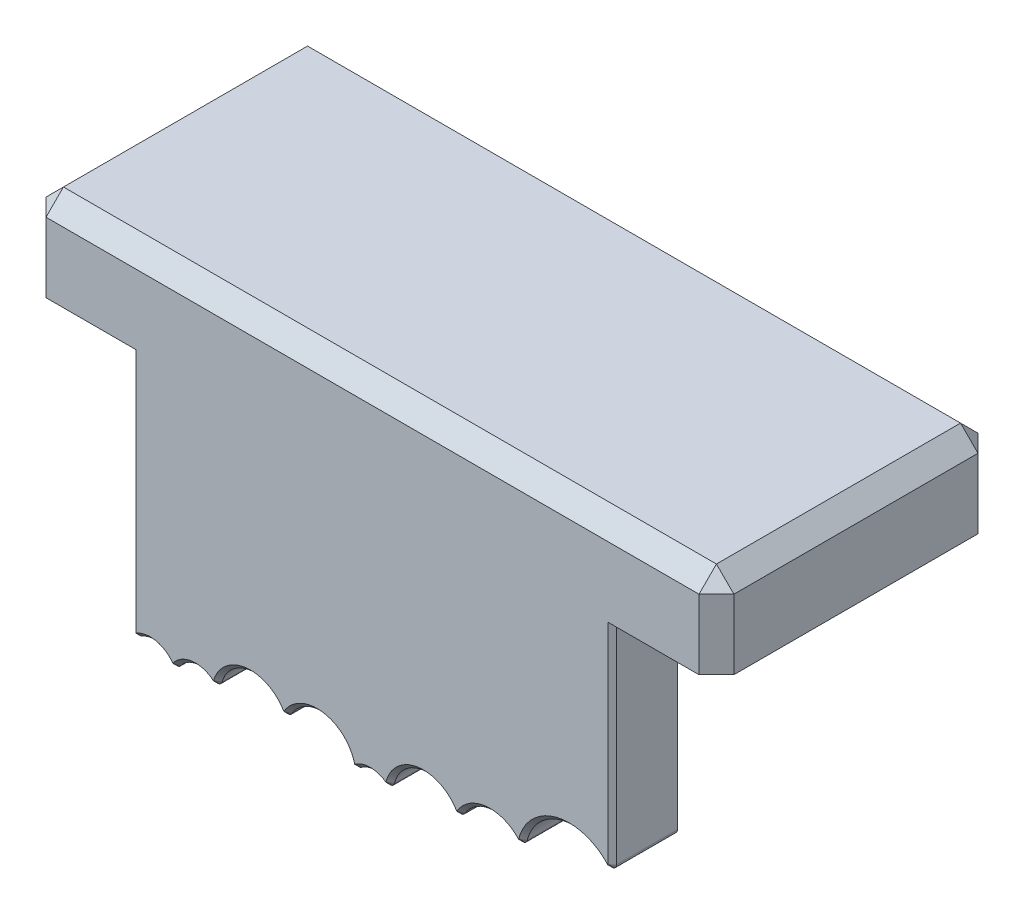
SolidWorks part; units mm, degrees
ref_plane "Front Plane" through (0, 0, 0) normal (0, 0, 1) x (1, 0, 0)
ref_plane "Top Plane" through (0, 0, 0) normal (0, 1, 0) x (1, 0, 0)
ref_plane "Right Plane" through (0, 0, 0) normal (1, 0, 0) x (0, 0, -1)
sketch "Sketch1" plane through (0, 0, 0) normal (0, 1, 0) x (1, 0, 0)
  point P0 (0, 0)
  point P1 (38.8013, -7.1245)
  line B0 (28.37, 45.6802) -> (28.37, 0) construction
  line B1 (28.37, 0) -> (39.45, 0) construction
  line B2 (39.45, 0) -> (39.45, 39.05) construction
  line B3 (39.45, 39.05) -> (36.7, 40.8) construction
  line B4 (36.7, 40.8) -> (36.7, 59.75) construction
  line B5 (36.7, 59.75) -> (32.77, 59.75) construction
  line B6 (32.77, 59.75) -> (32.77, 45.6802) construction
  line B7 (32.77, 45.6802) -> (28.37, 45.6802) construction
  line B8 (-28.37, 0) -> (-28.37, 45.6802) construction
  line B9 (-28.37, 45.6802) -> (-32.77, 45.6802) construction
  line B10 (-32.77, 45.6802) -> (-32.77, 59.75) construction
  line B11 (-32.77, 59.75) -> (-36.7, 59.75) construction
  line B12 (-36.7, 59.75) -> (-36.7, 40.8) construction
  line B13 (-36.7, 40.8) -> (-39.45, 39.05) construction
  line B14 (-39.45, 39.05) -> (-39.45, 0) construction
  line B15 (-39.45, 0) -> (-28.37, 0) construction
  line B16 (28.37, 0) -> (-28.37, 0) construction
  circle B17 centre (34.45, 9.5) radius 2.95 construction
  circle B18 centre (34.45, 25.5) radius 2.95 construction
  circle B19 centre (-34.45, 9.5) radius 2.95 construction
  circle B20 centre (-34.45, 25.5) radius 2.95 construction
sketch_block_instance "Block1-1"
sketch_block "Block1"
sketch "Sketch2" plane through (0, 0, 0) normal (0, 0, 1) x (1, 0, 0)
  point P0 (-28.4528, 0)
  line B0 (-39.5328, 0) -> (-39.5328, -39.5) construction
  line B1 (-39.5328, -39.5) -> (-28.4528, -39.5) construction
  line B2 (-28.4528, -39.5) -> (-28.4528, 0) construction
  line B3 (-28.4528, 0) -> (-39.5328, 0) construction
  line B4 (39.3672, -39.5) -> (39.3672, 0) construction
  line B5 (39.3672, 0) -> (28.2872, 0) construction
  line B6 (28.2872, 0) -> (28.2872, -39.5) construction
  line B7 (28.2872, -39.5) -> (39.3672, -39.5) construction
  circle B8 centre (-34.5328, -11.75) radius 2.95 construction
  circle B9 centre (34.3672, -11.75) radius 2.95 construction
  circle B10 centre (-34.5328, -27.75) radius 2.95 construction
  circle B11 centre (34.3672, -27.75) radius 2.95 construction
sketch_block_instance "Block2-1"
sketch_block "Block2"
ref_plane "Plane1" through (0, -39.5, 0) normal (0, 1, 0) x (1, 0, 0)
sketch "Sketch3" plane through (0, 0, 0) normal (0, 1, 0) x (1, 0, 0)
  line L0 (-39.45, 0) -> (-39.45, 32)
  line L1 (-39.45, 39.05) -> (-39.45, 0) construction
  line L2 (-39.45, 32) -> (39.45, 32)
  line L3 (39.45, 0) -> (39.45, 39.05) construction
  line L4 (39.45, 32) -> (39.45, 0)
  line L5 (39.45, 0) -> (-39.45, 0)
  circle A0 centre (-34.45, 9.5) radius 2.375
  circle A1 centre (34.45, 9.5) radius 2.375
  circle A2 centre (-34.45, 25.5) radius 2.375
  circle A3 centre (34.45, 25.5) radius 2.375
  dimension "D2" = 4.75
  dimension "D1" = 32
extrude "Boss-Extrude1" add sketch "Sketch3" along normal blind 10 contours L2 L4 L5 L0
extrude "Cut-Extrude1" cut sketch "Sketch3<4>" along normal blind 8 contours A0 | A1 | A2 | A3
sketch "Sketch3<4>" plane through (0, 0, 0) normal (0, 1, 0) x (1, 0, 0) same geometry as "Sketch3"
sketch "Sketch4" plane through (0, 0, 0) normal (0, 0, 1) x (1, 0, 0)
  line L2 (-27.6528, -39.5) -> (-27.6528, 0)
  line L3 (-27.6528, -33.5) -> (-27.6528, 0)
  line L4 (-27.6528, 0) -> (27.4872, 0)
  line L5 (27.4872, 0) -> (27.4872, -39.5)
  line L6 (27.4872, 0) -> (27.4872, -33.5)
  line L7 (-27.6528, -33.5) -> (27.4872, -33.5)
  dimension "D3" = 33.5
  dimension "D1" = 0.8
  dimension "D2" = 0.8
extrude "Boss-Extrude2" add sketch "Sketch4" against normal blind 8
sketch "Sketch6" plane through (0, 0, 0) normal (0, 0, 1) x (1, 0, 0)
  line L1 (-28.0993, -30.9) -> (-28.4528, -30.9) construction
  line L2 (-28.4528, -39.5) -> (-28.4528, 0) construction
  line L3 (27.9337, -28.125) -> (28.2872, -28.125) construction
  line L4 (28.2872, 0) -> (28.2872, -39.5) construction
  line L7 (-27.6528, -33.5) -> (27.4872, -33.5) construction
  line L10 (-27.6528, -33.5) -> (27.4872, -33.5)
  line L12 (-27.6528, 0) -> (-27.6528, -33.5) construction
  line L14 (27.4872, -33.5) -> (27.4872, 0) construction
  line L23 (-27.6528, -33.5) -> (-27.6528, -28.1603)
  line L24 (27.4872, -24.1139) -> (27.4872, -33.5)
  circle A0 centre (-25.4993, -30.9) radius 2.6 construction
  circle A1 centre (-13.9921, -29.675) radius 3.825 construction
  circle A2 centre (-6.3421, -29.675) radius 3.825 construction
  circle A3 centre (-0.2509, -31.075) radius 2.425 construction
  circle A4 centre (5.8403, -29.675) radius 3.825 construction
  circle A5 centre (13.4903, -29.675) radius 3.825 construction
  circle A6 centre (22.5587, -28.125) radius 5.375 construction
  arc A7 (-23.3055, -29.326) -> (-26.8944, -28.5884) centre (-25.4993, -30.9) ccw
  arc A8 (-10.5993, -27.7015) -> (-17.7631, -28.5864) centre (-13.9921, -29.675) ccw
  arc A9 (-2.5268, -28.7537) -> (-9.7349, -27.7015) centre (-6.3421, -29.675) ccw
  arc A10 (1.243, -29.0394) -> (-1.7449, -29.0394) centre (-0.2509, -31.075) ccw
  arc A11 (9.233, -27.7015) -> (2.0249, -28.7537) centre (5.8403, -29.675) ccw
  arc A12 (16.389, -27.0287) -> (10.0975, -27.7015) centre (13.4903, -29.675) ccw
  arc A13 (26.6167, -24.4496) -> (17.2436, -26.8115) centre (22.5587, -28.125) ccw
  circle A14 centre (-25.4993, -30.9) radius 2.7 construction
  circle A15 centre (-13.9921, -29.675) radius 3.925 construction
  circle A16 centre (-6.3421, -29.675) radius 3.925 construction
  circle A17 centre (-0.2509, -31.075) radius 2.525 construction
  circle A18 centre (5.8403, -29.675) radius 3.925 construction
  circle A19 centre (13.4903, -29.675) radius 3.925 construction
  circle A20 centre (22.5587, -28.125) radius 5.475 construction
  arc A22 (-10.5993, -27.7015) -> (-9.7349, -27.7015) centre (-10.1671, -27.4501) ccw
  arc A23 (-2.5268, -28.7537) -> (-1.7449, -29.0394) centre (-2.0407, -28.6363) ccw
  arc A24 (1.243, -29.0394) -> (2.0249, -28.7537) centre (1.5389, -28.6363) ccw
  arc A25 (9.233, -27.7015) -> (10.0975, -27.7015) centre (9.6653, -27.4501) ccw
  arc A26 (16.389, -27.0287) -> (17.2436, -26.8115) centre (16.7582, -26.6916) ccw
  arc A27 (26.6167, -24.4496) -> (27.4872, -24.1139) centre (26.9872, -24.1139) ccw
  arc A28 (-27.6528, -28.1603) -> (-26.8944, -28.5884) centre (-27.1528, -28.1603) ccw
  circle A29 centre (-20.2993, -30.9) radius 2.6 construction
  arc A30 (-18.5647, -28.8309) -> (-22.493, -29.326) centre (-20.2993, -30.9) ccw
  arc A31 (-18.5647, -28.8309) -> (-17.7631, -28.5864) centre (-18.2435, -28.4477) ccw
  arc A32 (-23.3055, -29.326) -> (-22.493, -29.326) centre (-22.8993, -29.0345) ccw
  circle A33 centre (-20.2993, -30.9) radius 2.7 construction
  dimension "D1" = 10.75
  dimension "D2" = 7.65
  dimension "D3" = 7.65
  dimension "D4" = 4.85
  dimension "D5" = 7.65
  dimension "D6" = 7.65
  dimension "D7" = 5.2
  dimension "D8" = 0.1
  dimension "D11" = 0.1
  dimension "D15" = 1
extrude "Cut-Extrude2" cut sketch "Sketch6" against normal up to next
fillet "Fillet1" radius 8 1 edges at (-0.0828, 0, -8)
chamfer "Chamfer1" distance 2 angle 45 8 edges at (0, 10, -32) (39.45, 5, -32) (39.45, 10, -16) (39.45, 5, 0) (0, 10, 0) (-39.45, 5, -32) (-39.45, 10, -16) (-39.45, 5, 0)
chamfer "Chamfer2" distance 0.5 angle 45 40 edges at (27.4872, -2.3431, -10.3431) (27.4872, -16.0569, -8) (27.1671, -24.5804, -8) (21.2209, -22.816, -8) (16.8814, -27.1762, -8) (13.0729, -25.7723, -8) (9.6653, -27.9501, -8) (5.2733, -25.7912, -8) (1.7105, -29.1059, -8) (-0.2509, -28.55, -8) (-2.2124, -29.1059, -8) (-5.7752, -25.7912, -8) (-10.1671, -27.9501, -8) (-14.4732, -25.7796, -8) (-24.9557, -28.2553, -8) (-27.6528, -2.3431, -10.3431) (-27.3985, -28.5957, -8) (-27.6528, -18.0802, -8) (27.4872, -12.0569, 0) (27.1671, -24.5804, 0) (21.2209, -22.816, 0) (16.8814, -27.1762, 0) (13.0729, -25.7723, 0) (9.6653, -27.9501, 0) (5.2733, -25.7912, 0) (1.7105, -29.1059, 0) (-0.2509, -28.55, 0) (-2.2124, -29.1059, 0) (-5.7752, -25.7912, 0) (-10.1671, -27.9501, 0) (-14.4732, -25.7796, 0) (-24.9557, -28.2553, 0) (-27.3985, -28.5957, 0) (-27.6528, -14.0802, 0) (-18.0976, -28.9259, -8) (-20.6369, -28.2212, -8) (-22.8993, -29.5345, -8) (-18.0976, -28.9259, 0) (-20.6369, -28.2212, 0) (-22.8993, -29.5345, 0)
equation "\"D2@Sketch4\"=\"D1@Sketch4\""
